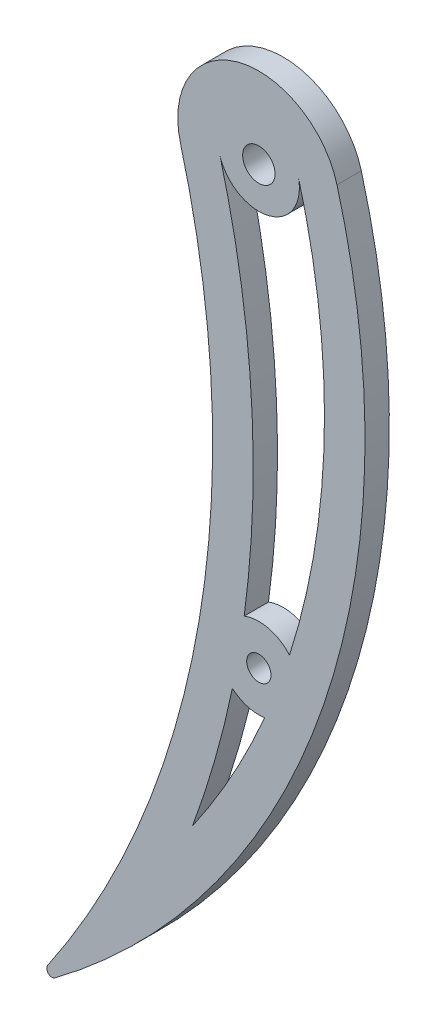
SolidWorks part; units mm, degrees
material "1060 Alloy"
ref_plane "Front Plane" through (0, 0, 0) normal (0, 0, 1) x (1, 0, 0)
ref_plane "Top Plane" through (0, 0, 0) normal (0, 1, 0) x (1, 0, 0)
ref_plane "Right Plane" through (0, 0, 0) normal (1, 0, 0) x (0, 0, -1)
sketch "Sketch1" plane through (0, 0, 0) normal (0, 0, 1) x (1, 0, 0)
  line L0 (5.1445, 48.6362) -> (5.1445, -5.1638)
  line L1 (-21.7555, -51.7438) -> (5.1445, -5.1638)
  line L2 (-17.4256, -54.2443) -> (10.1445, -6.5038)
  line L3 (0.1445, 48.6362) -> (0.1445, -5.1638)
  line L4 (10.1445, 48.6362) -> (10.1445, -5.1638)
  line L5 (10.1445, 48.6362) -> (10.1445, -6.5038)
  line L6 (-26.0853, -49.2433) -> (0.1445, -3.8237)
  line L7 (0.1445, 48.6362) -> (0.1445, -3.8237)
  circle A0 centre (5.1445, 48.6362) radius 2
  circle A1 centre (-21.7555, -51.7438) radius 2
  arc A2 (-17.4256, -54.2443) -> (-26.0853, -49.2433) centre (-21.7555, -51.7438) cw
  arc A3 (0.1445, 48.6362) -> (10.1445, 48.6362) centre (5.1445, 48.6362) cw
  circle A4 centre (5.1445, -5.1638) radius 1.5
  arc A5 (10.1445, 48.6362) -> (0.1445, 48.6362) centre (5.1445, 48.6362) ccw
  circle A6 centre (-95.2141, 21.7362) radius 99.0802
  arc A7 (0.1445, -5.1638) -> (10.1445, -5.1638) centre (5.1445, -5.1638) ccw
  circle A8 centre (5.9967, -2.4738) radius 104.0661
  circle A9 centre (-95.2141, 21.7362) radius 108.8802
  dimension "D2" = 4
  dimension "D3" = 4
  dimension "D1" = 3
extrude "Extrude1" add sketch "Sketch1" along normal blind 3 contours A7 L3 L6 A2 L2 A1 | A2 A9 L2 | L5 A9 A3 L4 | A3 A9 A6 A7 A4 A0 L4 | L2 A9 A7 | A7 A9 L5 region at (6.16, 21.4167, 0) region at (-9.5246, -32.956, 0) region at (-2.7557, -31.6611, 0) region at (9.716, -7.2082, 0) region at (10.1257, -5.6796, 0) region at (11.555, 21.7384, 0)
sketch "Sketch3" plane through (0, 0, 0) normal (0, 0, -1) x (-1, 0, 0)
  circle A0 centre (-5.1445, -5.1638) radius 7.5 construction
  arc A1 (4.5159, 46.0523) -> (-14.7839, 51.2976) centre (-5.1445, 48.6362) ccw
  arc A2 (19.9834, -50.8165) -> (-14.7839, 51.2976) centre (77.6238, 25.7843) cw
  circle A3 centre (21.7555, -51.7438) radius 2 construction
  arc A4 (20.9096, -49.9314) -> (4.5159, 46.0523) centre (117.2126, 15.9087) cw
  arc A5 (19.9834, -50.8165) -> (20.9096, -49.9314) centre (20.3737, -50.2978) ccw
  arc M1 (-9.8312, 50.3783) -> (18.5686, -55.5965) centre (95.2141, 21.7362) ccw
  arc M2 (18.5686, -55.5965) -> (26.0853, -49.2433) centre (21.7555, -51.7438) ccw
  arc M3 (26.0853, -49.2433) -> (-0.1445, 48.6362) centre (95.2141, 21.7362) cw
  arc M4 (-0.1445, 48.6362) -> (-9.8312, 50.3783) centre (-5.1445, 48.6362) ccw
  circle M5 centre (21.7555, -51.7438) radius 2
  dimension "D1" = 15
  dimension "D2" = 20
extrude "Cut-Extrude1" cut sketch "Sketch3" against normal blind 10 contours A4 A2 M5 M1 M2 M3 region at (-15.9387, -38.3925, 0)
extrude "Boss-Extrude1" add sketch "Sketch3<3>" against normal blind 3 contours A4 A1 A2 M3 M1 M4 | A5 M5 region at (0.2001, 9.8384, 0) region at (-20.5766, -50.5101, 0)
sketch "Sketch3<3>" plane through (0, 0, 0) normal (0, 0, -1) x (-1, 0, 0) same geometry as "Sketch3"
sketch "Sketch4" plane through (0, 0, 0) normal (0, 0, -1) x (-1, 0, 0)
  arc A5 (-5.8494, -10.1138) -> (-1.879, -8.9501) centre (-5.1445, -5.1638) ccw
  arc A6 (-9.9642, 49.9669) -> (-0.363, 50.0981) centre (-5.1445, 48.6362) ccw
  arc A7 (-3.3338, -0.5032) -> (-8.9242, -1.8905) centre (-5.1445, -5.1638) ccw
  arc A8 (-1.879, -8.9501) -> (3.0469, -26.1266) centre (117.2126, 15.9087) ccw
  arc A9 (-5.8494, -10.1138) -> (3.0469, -26.1266) centre (77.6238, 25.7843) ccw
  arc A10 (-0.3143, 47.3443) -> (3.0469, -26.1266) centre (117.2126, 15.9087) ccw
  arc A11 (-0.3143, 47.3443) -> (-9.9642, 49.9669) centre (-5.1445, 48.6362) ccw
  arc A12 (-9.9642, 49.9669) -> (3.0469, -26.1266) centre (77.6238, 25.7843) ccw
  arc A13 (-0.3143, 47.3443) -> (-3.3338, -0.5032) centre (117.2126, 15.9087) ccw
  arc A14 (-0.3143, 47.3443) -> (-0.363, 50.0981) centre (-5.1445, 48.6362) ccw
  arc A15 (-9.9642, 49.9669) -> (-8.9242, -1.8905) centre (77.6238, 25.7843) ccw
  dimension "D2" = 5
  dimension "D1" = 5
extrude "Cut-Extrude2" cut sketch "Sketch4" against normal blind 5 contours A6 A15 A7 A13 | A5 A9 A8 region at (1.6968, -15.4545, 0) region at (7.9618, 23.9826, 0)
move or copy body "Body-Move/Copy1" [suppressed] bodies to move or copy 106
move or copy body "Body-Move/Copy2" [suppressed] bodies to move or copy 106
